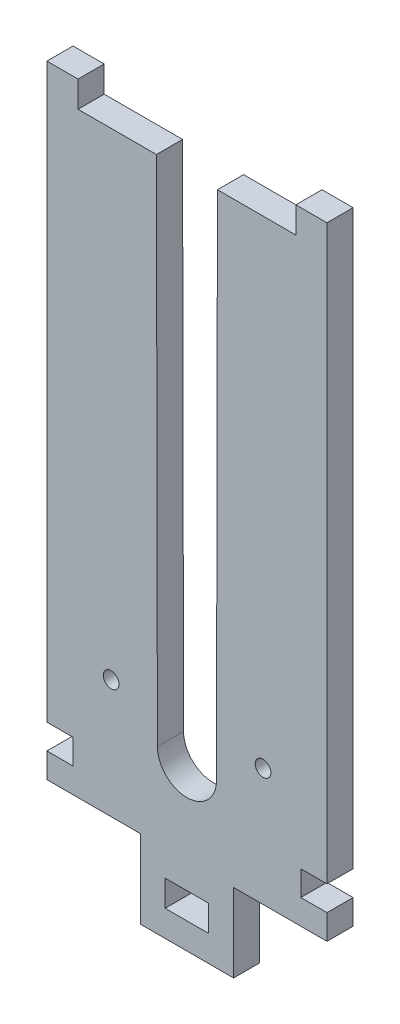
SolidWorks part; units mm, degrees
ref_plane "Front Plane" through (0, 0, 0) normal (0, 0, 1) x (1, 0, 0)
ref_plane "Top Plane" through (0, 0, 0) normal (0, 1, 0) x (1, 0, 0)
ref_plane "Right Plane" through (0, 0, 0) normal (1, 0, 0) x (0, 0, -1)
sketch "Sketch1" plane through (0, 0, 0) normal (0, 0, 1) x (1, 0, 0)
  line L1 (0, 0) -> (57.15, 0)
  line L2 (0, 0) -> (0, 127)
  line L3 (0, 127) -> (57.15, 127)
  line L4 (57.15, 0) -> (57.15, 127)
  dimension "D1" = 57.15
  dimension "D2" = 127
extrude "Boss-Extrude3" add sketch "Sketch1" along normal blind 5.334
sketch "Sketch3" plane through (0, 0, 5.334) normal (0, 0, 1) x (1, 0, 0)
  line L0 (22.352, 127) -> (0, 127)
  line L1 (57.15, 127) -> (0, 127) construction
  line L2 (57.15, 127) -> (34.798, 127)
  line L3 (28.575, 0) -> (28.575, 16.51) construction
  line L4 (0, 0) -> (57.15, 0) construction
  line L5 (34.798, 127) -> (34.6018, 22.479)
  line L6 (22.352, 127) -> (22.5482, 22.479)
  line L7 (28.575, 22.479) -> (28.575, 16.51)
  circle A0 centre (28.575, 22.479) radius 6.0268
  line M9 (57.15, 127) -> (0, 127)
  dimension "D1" = 22.352
  dimension "D2" = 22.352
  dimension "D3" = 16.51
  dimension "D4" = 5.969
extrude "Cut-Extrude2" cut sketch "Sketch3" against normal through all contours A0 L5 L6 M9 | A0 region at (28.575, 77.3496, 5.334) region at (28.575, 16.4692, 5.334)
sketch "Sketch8" plane through (0, 0, 0) normal (0, -1, 0) x (1, 0, 0)
  line L0 (0, 5.334) -> (57.15, 5.334) construction
  line L1 (57.15, 0) -> (38.1, 0)
  line L2 (57.15, 0) -> (57.15, 5.334)
  line L3 (57.15, 5.334) -> (38.1, 5.334)
  line L4 (38.1, 0) -> (38.1, 5.334)
  line L5 (0, 0) -> (57.15, 0) construction
  line L6 (19.05, 0) -> (0, 0)
  line L7 (19.05, 0) -> (19.05, 5.334)
  line L8 (19.05, 5.334) -> (0, 5.334)
  line L9 (0, 0) -> (0, 5.334)
  line L10 (38.1, 5.334) -> (19.05, 5.334) construction
extrude "Cut-Extrude6" cut sketch "Sketch8" against normal blind 5.334 contours L4 L3 L2 L1
extrude "Cut-Extrude7" cut sketch "Sketch8<5>" against normal blind 5.334
sketch "Sketch8<5>" plane through (0, 0, 0) normal (0, -1, 0) x (1, 0, 0) same geometry as "Sketch8"
sketch "Sketch16" plane through (0, 127, 0) normal (0, 1, 0) x (1, 0, 0)
  line L1 (34.798, 0) -> (57.15, 0)
  line L2 (34.798, 0) -> (34.798, -5.334)
  line L3 (34.798, -5.334) -> (57.15, -5.334)
  line L4 (57.15, 0) -> (57.15, -5.334)
  line L5 (0, 0) -> (22.352, 0)
  line L6 (0, 0) -> (0, -5.334)
  line L7 (0, -5.334) -> (22.352, -5.334)
  line L8 (22.352, 0) -> (22.352, -5.334)
extrude "Boss-Extrude4" add sketch "Sketch16" along normal blind 5.334
sketch "Sketch32" plane through (0, 132.334, 0) normal (0, 1, 0) x (1, 0, 0)
  line L0 (0, -5.334) -> (22.352, -5.334) construction
  line L1 (0, 0) -> (6.35, 0)
  line L2 (0, 0) -> (0, -5.334)
  line L3 (0, -5.334) -> (6.35, -5.334)
  line L4 (6.35, 0) -> (6.35, -5.334)
  line L5 (34.798, -5.334) -> (57.15, -5.334) construction
  line L6 (57.15, 0) -> (50.8, 0)
  line L7 (57.15, 0) -> (57.15, -5.334)
  line L8 (57.15, -5.334) -> (50.8, -5.334)
  line L9 (50.8, 0) -> (50.8, -5.334)
  line L11 (6.35, 0) -> (22.352, 0)
  line L12 (6.35, 0) -> (6.35, -5.334)
  line L13 (6.35, -5.334) -> (22.352, -5.334)
  line L14 (22.352, 0) -> (22.352, -5.334)
  line L15 (34.798, -5.334) -> (50.8, -5.334)
  line L16 (34.798, -5.334) -> (34.798, 0)
  line L17 (34.798, 0) -> (50.8, 0)
  line L18 (50.8, -5.334) -> (50.8, 0)
  line M4 (0, -5.334) -> (22.352, -5.334)
  line M5 (22.352, -5.334) -> (22.352, 0)
  line M6 (22.352, 0) -> (0, 0)
  dimension "D1" = 6.35
  dimension "D2" = 6.35
extrude "Cut-Extrude13" cut sketch "Sketch32" against normal blind 5.334 contours L4 M6 M4 M5 | L17 L16 L15 L9 region at (14.351, 132.334, 2.667) region at (42.799, 132.334, 2.667)
sketch "Sketch35" plane through (0, 0, 5.334) normal (0, 0, 1) x (1, 0, 0)
  circle A0 centre (13.1076, 29.5507) radius 1.6
  circle A1 centre (44.1073, 29.4071) radius 1.6
extrude "Cut-Extrude15" cut sketch "Sketch35" against normal through all
sketch "Sketch36" plane through (0, 0, 0) normal (0, -1, 0) x (1, 0, 0)
  line L1 (38.1, 0) -> (19.05, 0)
  line L2 (38.1, 0) -> (38.1, 5.334)
  line L3 (38.1, 5.334) -> (19.05, 5.334)
  line L4 (19.05, 0) -> (19.05, 5.334)
extrude "Boss-Extrude5" add sketch "Sketch36" along normal blind 10.668
sketch "Sketch37" plane through (0, 0, 0) normal (0, 0, -1) x (-1, 0, 0)
  line L0 (-19.05, -10.668) -> (-38.1, -10.668) construction
  line L1 (-33.02, 0) -> (-24.13, 0)
  line L2 (-33.02, 0) -> (-33.02, -5.334)
  line L3 (-33.02, -5.334) -> (-24.13, -5.334)
  line L4 (-24.13, 0) -> (-24.13, -5.334)
  line L5 (-19.05, 5.334) -> (-19.05, -10.668) construction
  dimension "D1" = 5.334
  dimension "D2" = 5.334
  dimension "D3" = 8.89
  dimension "D4" = 5.08
extrude "Cut-Extrude16" cut sketch "Sketch37" against normal through all
sketch "Sketch38" plane through (0, 0, 0) normal (0, 0, -1) x (-1, 0, 0)
  line L0 (-57.15, 5.334) -> (0, 5.334) construction
  line L1 (-28.575, 5.334) -> (-28.575, 13.6237) construction
  line L2 (-57.15, 5.334) -> (-57.15, 132.334) construction
  line L3 (-57.15, 10.414) -> (-51.816, 10.414)
  line L4 (-57.15, 10.414) -> (-57.15, 15.494)
  line L5 (-57.15, 15.494) -> (-51.816, 15.494)
  line L6 (-51.816, 10.414) -> (-51.816, 15.494)
  line L7 (-5.334, 10.414) -> (-5.334, 15.494)
  line L8 (0, 15.494) -> (-5.334, 15.494)
  line L9 (0, 10.414) -> (0, 15.494)
  line L10 (0, 10.414) -> (-5.334, 10.414)
  dimension "D1" = 5.334
  dimension "D2" = 5.08
  dimension "D3" = 5.08
extrude "Cut-Extrude17" cut sketch "Sketch38" against normal through all
equation "\"Foamcore\"= .1875in"
equation "\"Mdf\"= .21in"
equation "\"Gmaterial\"= \"Mdf\""
equation "\"D1@Boss-Extrude3\"= \"Gmaterial\""
equation "\"D1@Cut-Extrude6\"= \"Gmaterial\""
equation "\"D1@Cut-Extrude7\"=\"Gmaterial\""
equation "\"D1@Boss-Extrude4\"= \"Gmaterial\""
equation "\"D3@Sketch3\"= .65in"
equation "\"D1@Cut-Extrude13\"=\"Gmaterial\""
